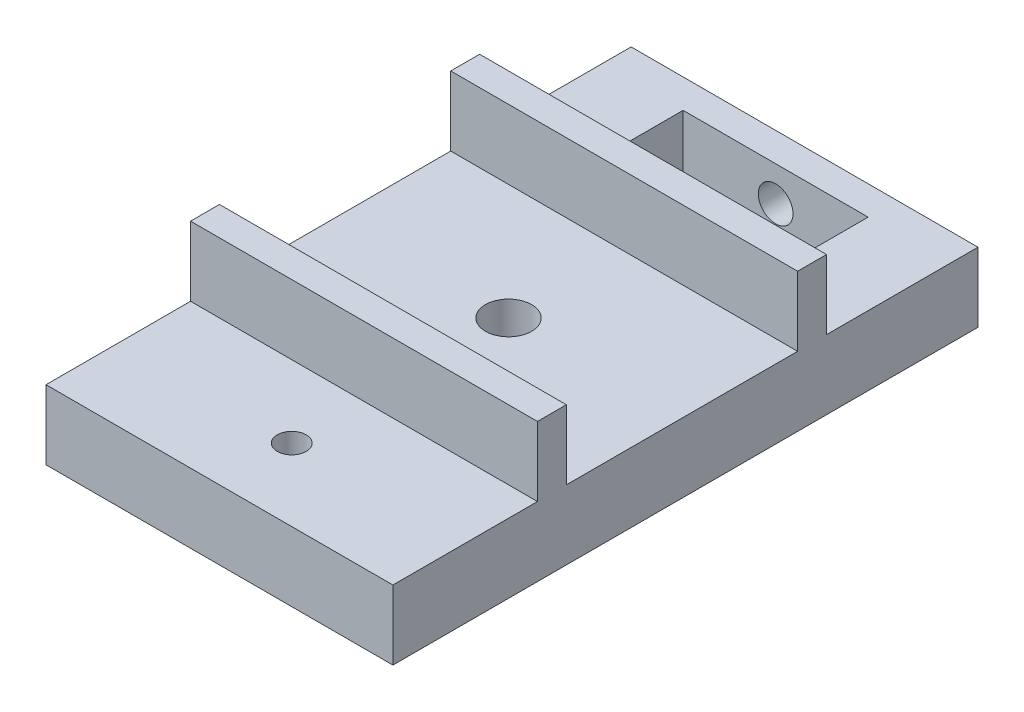
SolidWorks part; units mm, degrees
ref_plane "Front" through (0, 0, 0) normal (0, 0, 1) x (1, 0, 0)
ref_plane "Top" through (0, 0, 0) normal (0, 1, 0) x (1, 0, 0)
ref_plane "Right" through (0, 0, 0) normal (1, 0, 0) x (0, 0, -1)
sketch "Sketch1" plane through (0, 0, 0) normal (0, 1, 0) x (1, 0, 0)
  line L0 (0, -20) -> (0, -22.5)
  line L1 (0, 0) -> (-30, 0)
  line L2 (0, 0) -> (0, -20)
  line L3 (0, -20) -> (-30, -20)
  line L4 (-30, 0) -> (-30, -20)
  line L5 (0, -22.5) -> (-30, -22.5)
  line L6 (-30, -22.5) -> (-30, -20)
  line L7 (0, 0) -> (-7, 0)
  line L8 (-30, 0) -> (0, 0)
  line L9 (-30, 0) -> (-30, 2.5)
  line L10 (-30, 2.5) -> (0, 2.5)
  line L11 (0, 0) -> (0, 2.5)
  line L12 (-30, 0) -> (-23, 0)
  line L13 (-30, 2.5) -> (-30, 13.1)
  line L14 (-30, 13.1) -> (0, 13.1)
  line L15 (0, 13.1) -> (0, 2.5)
  line L16 (0, 13.1) -> (0, 15.6)
  line L17 (0, 15.6) -> (-30, 15.6)
  line L18 (-30, 15.6) -> (-30, 13.1)
  line L19 (-7, 0) -> (-7, 15.6)
  line L20 (-23, 0) -> (-23, 15.6)
  dimension "D1" = 20
  dimension "D2" = 2.5
  dimension "D3" = 2.5
  dimension "D4" = 30
  dimension "D5" = 7
  dimension "D6" = 7
  dimension "D7" = 10.6
  dimension "D8" = 2.5
extrude "Boss-Extrude1" add sketch "Sketch1" along normal blind 6 contours L1 L8 L4 L3 L2 | L6 L5 L0 L3 | L20 L1 L19 L10 | L19 L1 L11 L10 | L19 L10 L15 L14 | L19 L14 L16 L17 | L20 L14 L19 L17 | L14 L20 L17 L18 | L10 L20 L14 L13 | L8 L20 L10 L9 region at (-15, 0, 10) region at (-15, 0, 21.25) region at (-3.5, 0, -1.25) region at (-15, 0, -1.25) region at (-3.5, 0, -7.8) region at (-26.5, 0, -1.25) region at (-3.5, 0, -14.35) region at (-26.5, 0, -7.8) region at (-15, 0, -14.35) region at (-26.5, 0, -14.35)
extrude "Boss-Extrude2" add sketch "Sketch1<3>" along normal blind 12 contours L19 L1 L11 L10 | L20 L1 L19 L10 | L6 L5 L0 L3 | L8 L20 L10 L9 region at (-15, 0, 21.25) region at (-3.5, 0, -1.25) region at (-15, 0, -1.25) region at (-26.5, 0, -1.25)
sketch "Sketch1<3>" plane through (0, 0, 0) normal (0, 1, 0) x (1, 0, 0) same geometry as "Sketch1"
sketch "Sketch3" plane through (0, 0, -15.6) normal (0, 0, -1) x (-1, 0, 0)
  line L0 (30, 3) -> (23, 3)
  line L1 (30, 6) -> (30, 0) construction
  line L2 (23, 3) -> (15, 3)
  circle A0 centre (15, 3) radius 1.5
  dimension "D1" = 7
  dimension "D2" = 8
extrude "Cut-Extrude2" cut sketch "Sketch3" against normal blind 5 contours A0
sketch "Sketch4" plane through (0, 0, -2.5) normal (0, 0, -1) x (-1, 0, 0)
  line L0 (23, 3) -> (15, 3)
  line L1 (23, 6) -> (23, 0) construction
  line L3 (17.8868, 3) -> (16.4434, 5.5)
  line L4 (16.4434, 5.5) -> (13.5566, 5.5)
  line L5 (13.5566, 5.5) -> (12.1132, 3)
  line L6 (12.1132, 3) -> (13.5566, 0.5)
  line L7 (13.5566, 0.5) -> (16.4434, 0.5)
  line L8 (16.4434, 0.5) -> (17.8868, 3)
  circle A0 centre (15, 3) radius 2.5 construction
  dimension "D1" = 8
extrude "Cut-Extrude3" cut sketch "Sketch4" against normal blind 2.5 contours L7 L8 L3 L4 L5 L6 region at (-17.0989, 1.7882, -2.5)
ref_plane "Plane1" through (0, 0, 10) normal (0, 0, -1) x (-1, 0, 0)
sketch "Sketch2" plane through (0, 6, 0) normal (0, 1, 0) x (1, 0, 0)
  line L0 (-30, -10) -> (0, -10)
  line L1 (-30, 0) -> (-30, -20) construction
  line L2 (0, 0) -> (0, -20) construction
  circle A0 centre (-15, -10) radius 2
extrude "Cut-Extrude1" cut sketch "Sketch2" against normal through all contours L0 A0 | L0 A0 region at (-15, 6, 9.1512) region at (-15, 6, 10.8488)
sketch "Sketch5" plane through (0, 0, 0) normal (0, -1, 0) x (1, 0, 0)
  line L0 (-30, 22.5) -> (-25, 22.5)
  line L1 (-30, 22.5) -> (0, 22.5)
  line L2 (-30, 22.5) -> (-30, 32.5)
  line L3 (0, 22.5) -> (0, 32.5)
  line L4 (-30, 32.5) -> (0, 32.5)
  line L5 (-25, 22.5) -> (-25, 32.5)
  line L6 (-25, 32.5) -> (-5, 32.5)
  line L7 (-5, 32.5) -> (-5, 22.5)
  line L8 (-5, 22.5) -> (0, 22.5)
  line L9 (-30, 32.5) -> (-30, 35)
  line L10 (-30, 35) -> (0, 35)
  line L11 (0, 35) -> (0, 32.5)
  line L12 (-15, 35) -> (-15, 22.5)
  circle A0 centre (-15, 28.75) radius 1.25
  line M7 (0, 22.5) -> (-30, 22.5)
  dimension "D1" = 10
  dimension "D2" = 5
  dimension "D3" = 5
  dimension "D4" = 2.5
extrude "Boss-Extrude3" add sketch "Sketch5" against normal blind 6 contours L5 L4 L2 M7 | L11 L10 L9 L4 | L4 L7 L3 M7 | L7 L4 L5 L1 | A0 L12 L4 L5 M7 | L12 L10 L9 L4 region at (-27.5, 0, 27.5) region at (-20.1125, 0, 27.4685) region at (-22.5, 0, 33.75) region at (-9.8875, 0, 27.4685) region at (-2.5, 0, 27.5) region at (-7.5, 0, 33.75)
